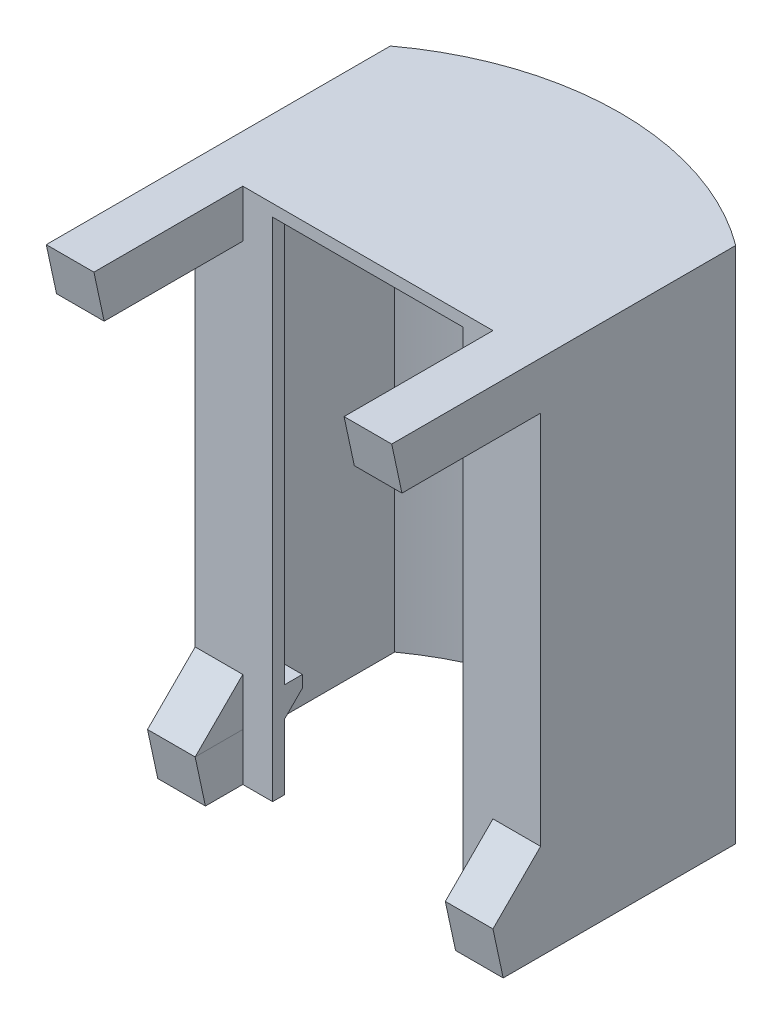
SolidWorks part; units mm, degrees
ref_plane "Front Plane" through (0, 0, 0) normal (0, 0, 1) x (1, 0, 0)
ref_plane "Top Plane" through (0, 0, 0) normal (0, 1, 0) x (1, 0, 0)
ref_plane "Right Plane" through (0, 0, 0) normal (1, 0, 0) x (0, 0, -1)
sketch "Sketch1" plane through (0, 0, 0) normal (0, 1, 0) x (1, 0, 0)
  line L0 (-29, -15) -> (-29, 15.7626)
  line L1 (-27.5, -15) -> (-16, -15)
  line L2 (-27.5, -15) -> (-27.5, 15)
  line L3 (29, -15) -> (29, 15.7626)
  line L4 (27.5, -15) -> (27.5, 15)
  line L5 (-27.5, -15) -> (27.5, 15) construction
  line L6 (-27.5, 15) -> (27.5, -15) construction
  line L8 (16, -15) -> (27.5, -15)
  line L9 (-27.5, -17) -> (-16, -17)
  line L10 (-16, -15) -> (-16, -17)
  line L12 (27.5, -17) -> (29, -17)
  line L13 (27.5, -17) -> (16, -17)
  line L14 (16, -15) -> (16, -17)
  line L15 (-29, -15) -> (-29, -17)
  line L16 (-29, -17) -> (-27.5, -17)
  line L17 (29, -17) -> (29, -15)
  arc A0 (-27.5, 15) -> (27.5, 15) centre (0, -23.3475) cw
  arc A1 (-29, 15.7626) -> (29, 15.7626) centre (0, -23.3475) cw
  point P0 (0, 0)
  dimension "D1" = 55
  dimension "D2" = 30
  dimension "D3" = 2
  dimension "D4" = 2
  dimension "D5" = 32
  dimension "D6" = 1.5
extrude "Boss-Extrude1" add sketch "Sketch1" along normal blind 85
sketch "Sketch3" plane through (0, 85, 0) normal (0, 1, 0) x (1, 0, 0)
  line L0 (-16, -17) -> (16, -17)
  line L10 (27.5, 15) -> (27.5, -15)
  line L11 (27.5, -15) -> (16, -15)
  line L12 (16, -15) -> (16, -17)
  line L13 (16, -17) -> (29, -17)
  line L14 (29, -17) -> (29, 15.7626)
  line L15 (-29, 15.7626) -> (-29, -17)
  line L16 (-29, -17) -> (-16, -17)
  line L17 (-16, -17) -> (-16, -15)
  line L18 (-16, -15) -> (-27.5, -15)
  line L19 (-27.5, -15) -> (-27.5, 15)
  line L23 (16, -17) -> (29, -17)
  line L24 (29, -17) -> (29, 15.7626)
  line L25 (-29, 15.7626) -> (-29, -17)
  line L26 (-29, -17) -> (-16, -17)
  arc A2 (27.5, 15) -> (-27.5, 15) centre (0, -23.3475) ccw
  arc A3 (29, 15.7626) -> (-29, 15.7626) centre (0, -23.3475) ccw
  arc A5 (29, 15.7626) -> (-29, 15.7626) centre (0, -23.3475) ccw
  dimension "D1" = 0
extrude "Boss-Extrude3" add sketch "Sketch3" along normal blind 2
sketch "Sketch4" plane through (0, 0, 17) normal (0, 0, 1) x (1, 0, 0)
  line L1 (-29, 87) -> (-21, 87)
  line L2 (-29, 87) -> (-29, 79)
  line L3 (-29, 79) -> (-21, 79)
  line L4 (-21, 87) -> (-21, 79)
  line L5 (29, 87) -> (21, 87)
  line L6 (29, 87) -> (29, 79)
  line L7 (29, 79) -> (21, 79)
  line L8 (21, 87) -> (21, 79)
  dimension "D1" = 8
  dimension "D2" = 8
  dimension "D3" = 8
  dimension "D4" = 8
extrude "Boss-Extrude4" add sketch "Sketch4" along normal blind 25
sketch "Sketch5" plane through (0, 0, 17) normal (0, 0, 1) x (1, 0, 0)
  line L1 (-29, 0) -> (-21, 0)
  line L2 (-29, 0) -> (-29, 8)
  line L3 (-29, 8) -> (-21, 8)
  line L4 (-21, 0) -> (-21, 8)
  line L5 (29, 0) -> (21, 0)
  line L6 (29, 0) -> (29, 8)
  line L7 (29, 8) -> (21, 8)
  line L8 (21, 0) -> (21, 8)
  dimension "D1" = 8
  dimension "D2" = 8
  dimension "D3" = 8
  dimension "D4" = 8
extrude "Boss-Extrude5" add sketch "Sketch5" along normal blind 8
sketch "Sketch6" plane through (29, 0, 0) normal (1, 0, 0) x (0, 0, -1)
  line L0 (-42, 87) -> (-25, 8)
  line L1 (-25, 8) -> (-22.5325, -3.4667)
  line L2 (-22.5325, -3.4667) -> (-79.8922, -33.861)
  line L3 (-79.8922, -33.861) -> (-91.2866, 63.0921)
  line L4 (-91.2866, 63.0921) -> (-70.492, 113.2372)
  line L5 (-70.492, 113.2372) -> (-29.5564, 113.2372)
  line L6 (-29.5564, 113.2372) -> (-42, 87)
extrude "Cut-Extrude1" cut sketch "Sketch6" against normal through all
sketch "Sketch7" plane through (29, 0, 0) normal (1, 0, 0) x (0, 0, -1)
  line L0 (-25, 8) -> (-17, 16)
  line L1 (-17, 79) -> (-17, 8) construction
  line L2 (-17, 16) -> (-17, 8)
  line L3 (-17, 8) -> (-25, 8)
  dimension "D1" = 45
extrude "Boss-Extrude6" add sketch "Sketch7" against normal blind 8
sketch "Sketch8" plane through (-29, 0, 0) normal (-1, 0, 0) x (0, 0, 1)
  line L0 (25, 8) -> (17, 16)
  line L1 (17, 79) -> (17, 8) construction
  line L2 (17, 16) -> (17, 8)
  line L3 (17, 8) -> (25, 8)
  dimension "D1" = 45
extrude "Boss-Extrude7" add sketch "Sketch8" against normal blind 8 separate body
sketch "Sketch9" plane through (0, 0, 15) normal (0, 0, -1) x (-1, 0, 0)
  line L0 (-27.5, 85) -> (-27.5, 0) construction
  line L1 (-27.5, 14) -> (-16, 14)
  line L2 (-27.5, 14) -> (-27.5, 16)
  line L3 (-27.5, 16) -> (-16, 16)
  line L4 (-16, 14) -> (-16, 16)
  line L5 (-16, 85) -> (-16, 0) construction
  line L6 (-27.5, 0) -> (-16, 0) construction
  line L7 (27.5, 85) -> (27.5, 0) construction
  line L8 (27.5, 14) -> (16, 14)
  line L9 (27.5, 14) -> (27.5, 16)
  line L10 (27.5, 16) -> (16, 16)
  line L11 (16, 14) -> (16, 16)
  line L12 (16, 85) -> (16, 0) construction
  dimension "D1" = 2
  dimension "D2" = 14
extrude "Boss-Extrude8" add sketch "Sketch9" along normal blind 3
chamfer "Chamfer1" distance 3 angle 45 2 edges at (-21.75, 14, 15) (21.75, 14, 15)
